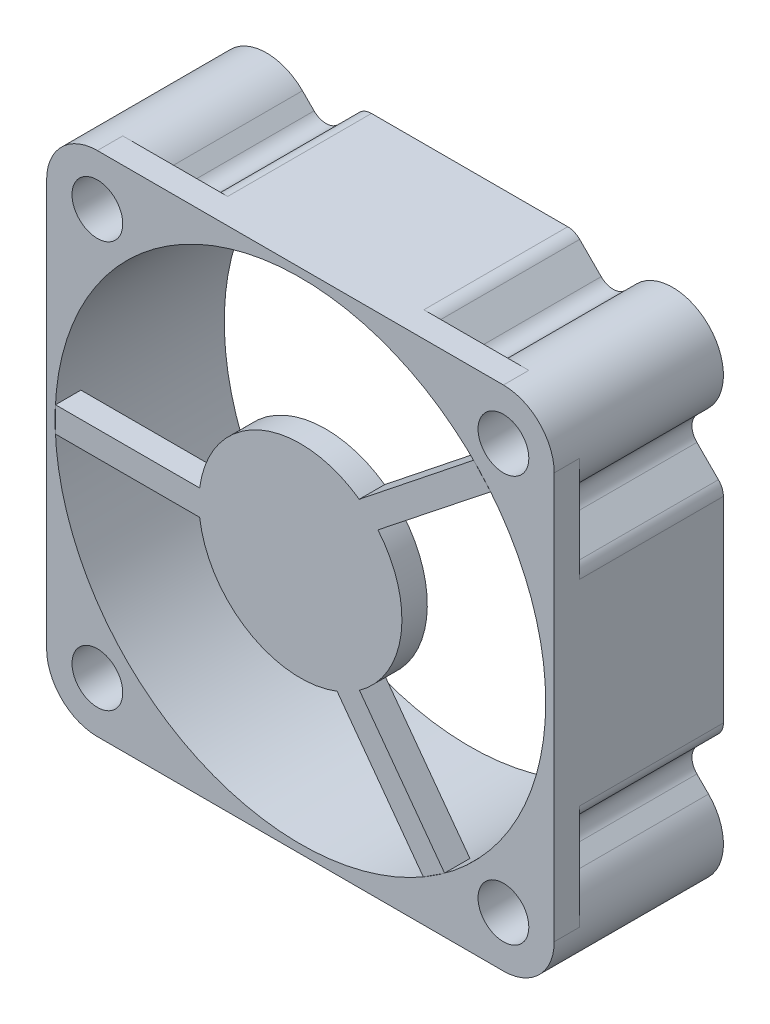
SolidWorks part; units mm, degrees
material "PBT Genel Kullanım"
ref_plane "Ön Düzlem" through (0, 0, 0) normal (0, 0, 1) x (1, 0, 0)
ref_plane "Üst Düzlem" through (0, 0, 0) normal (0, 1, 0) x (1, 0, 0)
ref_plane "Sağ Düzlem" through (0, 0, 0) normal (1, 0, 0) x (0, 0, -1)
sketch "Çizim1" plane through (0, 0, 0) normal (0, 0, 1) x (1, 0, 0)
  circle A0 centre (0, 0) radius 15
  dimension "D1" = 30
extrude "Yükseklik-Ekstrüzyon1" add sketch "Çizim1" along normal blind 10
sketch "Çizim3" plane through (0, 0, 10) normal (0, 0, 1) x (1, 0, 0)
  line L1 (-15, -15) -> (15, -15)
  line L2 (-15, -15) -> (-15, 15)
  line L3 (-15, 15) -> (15, 15)
  line L4 (15, -15) -> (15, 15)
  line L5 (-15, -15) -> (15, 15) construction
  line L6 (-15, 15) -> (15, -15) construction
  point P0 (0, 0)
  dimension "D1" = 30
  dimension "D2" = 30
extrude "Yükseklik-Ekstrüzyon2" add sketch "Çizim3" against normal blind 1.5
sketch "Çizim4" plane through (0, 0, 0) normal (0, 0, -1) x (-1, 0, 0)
  line L0 (0, 15) -> (15, 15) construction
  line L1 (-15, 15) -> (0, 15) construction
  line L2 (-15, 0) -> (-15, 15) construction
  line L3 (-15, -15) -> (-15, 0) construction
  line L4 (0, -15) -> (-15, -15) construction
  line L5 (15, -15) -> (0, -15) construction
  line L6 (15, 0) -> (15, -15) construction
  line L7 (15, 15) -> (15, 0) construction
  line L8 (0, 15) -> (15, 15)
  line L9 (-15, 15) -> (0, 15)
  line L10 (-15, 0) -> (-15, 15)
  line L11 (-15, -15) -> (-15, 0)
  line L12 (0, -15) -> (-15, -15)
  line L13 (15, -15) -> (0, -15)
  line L14 (15, 0) -> (15, -15)
  line L15 (15, 15) -> (15, 0)
extrude "Yükseklik-Ekstrüzyon3" add sketch "Çizim4" against normal blind 1.5
sketch "Çizim2" plane through (0, 0, 10) normal (0, 0, 1) x (1, 0, 0)
  circle A0 centre (0, 0) radius 14.5
  dimension "D1" = 29
extrude "Kes-Ekstrüzyon1" cut sketch "Çizim2" against normal blind 10
sketch "Çizim5" plane through (0, 0, 10) normal (0, 0, 1) x (1, 0, 0)
  circle A0 centre (0, 0) radius 6
  dimension "D1" = 12
extrude "Yükseklik-Ekstrüzyon4" add sketch "Çizim5" against normal blind 1.5 separate body
sketch "Çizim8" plane through (0, 0, 10) normal (0, 0, 1) x (1, 0, 0)
  line L0 (11.2438, 9.1557) -> (4.5817, 3.8741)
  line L1 (11.2438, 9.1557) -> (10.2378, 10.2683)
  line L2 (10.2378, 10.2683) -> (3.4776, 4.8894)
  circle A0 centre (0, 0) radius 14.5 construction
  circle A1 centre (0, 0) radius 6 construction
  circle A3 centre (0, 0) radius 6
  arc A4 (3.4776, 4.8894) -> (4.5817, 3.8741) centre (0, 0) ccw
  dimension "D1" = 1.5
  dimension "D2" = 1.5
  dimension "D3" = 0
extrude "Yükseklik-Ekstrüzyon7" add sketch "Çizim8" against normal blind 1.5
sketch "Çizim9" plane through (0, 0, 10) normal (0, 0, 1) x (1, 0, 0)
  line L0 (-14.4806, 0.75) -> (-5.9529, 0.75)
  line L1 (-14.4806, 0.75) -> (-14.4806, -0.75)
  line L2 (-14.4806, -0.75) -> (-5.9529, -0.75)
  line L6 (4.5817, 3.8741) -> (11.2438, 9.1557)
  line L7 (11.2438, 9.1557) -> (10.2378, 10.2683)
  line L8 (10.2378, 10.2683) -> (3.4776, 4.8894)
  line L9 (4.5817, 3.8741) -> (11.2438, 9.1557)
  line L10 (11.2438, 9.1557) -> (10.2378, 10.2683)
  line L11 (10.2378, 10.2683) -> (3.4776, 4.8894)
  circle A0 centre (0, 0) radius 14.5 construction
  arc A1 (3.4776, 4.8894) -> (4.5817, 3.8741) centre (0, 0) ccw construction
  arc A2 (3.4776, 4.8894) -> (-5.9529, 0.75) centre (0, 0) ccw
  arc A3 (3.4776, 4.8894) -> (4.5817, 3.8741) centre (0, 0) ccw
  arc A4 (-5.9529, -0.75) -> (4.5817, 3.8741) centre (0, 0) ccw
  dimension "D1" = 0.75
  dimension "D2" = 0
extrude "Yükseklik-Ekstrüzyon8" add sketch "Çizim9" against normal blind 1.5
sketch "Çizim10" plane through (0, 0, 10) normal (0, 0, 1) x (1, 0, 0)
  line L0 (8.5237, -11.7302) -> (3.49, -4.8806)
  line L1 (8.5237, -11.7302) -> (7.2662, -12.548)
  line L2 (7.2662, -12.548) -> (2.1704, -5.5937)
  line L9 (-5.9529, 0.75) -> (-14.4806, 0.75)
  line L10 (-14.4806, 0.75) -> (-14.4806, -0.75)
  line L11 (-14.4806, -0.75) -> (-5.9529, -0.75)
  line L12 (4.5817, 3.8741) -> (11.2438, 9.1557)
  line L13 (11.2438, 9.1557) -> (10.2378, 10.2683)
  line L14 (10.2378, 10.2683) -> (3.4776, 4.8894)
  circle A0 centre (0, 0) radius 14.5 construction
  arc A1 (-5.9529, -0.75) -> (4.5817, 3.8741) centre (0, 0) ccw construction
  arc A4 (3.4776, 4.8894) -> (-5.9529, 0.75) centre (0, 0) ccw
  arc A5 (-5.9529, -0.75) -> (4.5817, 3.8741) centre (0, 0) ccw
  arc A7 (2.1704, -5.5937) -> (3.49, -4.8806) centre (0, 0) ccw
  dimension "D1" = 1.5
  dimension "D2" = 1.5
  dimension "D3" = 0
extrude "Yükseklik-Ekstrüzyon9" add sketch "Çizim10" against normal blind 1.5
fillet "Radyus1" radius 3 8 edges at (-15, -15, 9.25) (-15, -15, 0.75) (15, -15, 9.25) (15, -15, 0.75) (15, 15, 0.75) (15, 15, 9.25) (-15, 15, 0.75) (-15, 15, 9.25)
sketch "Çizim11" plane through (0, 0, 10) normal (0, 0, 1) x (1, 0, 0)
  line L0 (-15, 12) -> (-15, -12) construction
  circle A0 centre (-12, 12) radius 1.5
  dimension "D3" = 3
  dimension "D1" = 3
  dimension "D2" = 3
extrude "Kes-Ekstrüzyon2" cut sketch "Çizim11" against normal blind 42.5
ref_plane "Düzlem1" through (0, 0, 0) normal (-1, 0, 0) x (0, 0, 1)
mirror "Aynalama1" about plane through (0, 0, 0) normal (-1, 0, 0) of "Kes-Ekstrüzyon2"
ref_plane "Düzlem2" through (0, 0, 0) normal (0, 1, 0) x (1, 0, 0)
mirror "Aynalama2" about plane through (0, 0, 0) normal (0, 1, 0) of "Aynalama1", "Kes-Ekstrüzyon2"
sketch "Sketch1" plane through (0, 0, 0) normal (0, 0, -1) x (-1, 0, 0)
  line L0 (-15, 0) -> (15, 0) construction
  line L1 (-15, 12) -> (-15, -12) construction
  line L2 (15, -12) -> (15, 12) construction
  line L3 (0, 15) -> (0, -15) construction
  line L4 (-12, -15) -> (12, -15) construction
  line L5 (-15, 6.2132) -> (-6.2132, 15) construction
  line L7 (12, 15) -> (-12, 15) construction
  line L8 (-8.4853, 12.7279) -> (-9.8787, 14.1213)
  line L9 (-12.7279, 8.4853) -> (-14.1213, 9.8787)
  line L10 (-8.4853, 12.7279) -> (-6.2132, 15)
  line L11 (-6.2132, 15) -> (-12, 15)
  line L12 (-12.7279, 8.4853) -> (-15, 6.2132)
  line L13 (-15, 6.2132) -> (-15, 12)
  line L14 (-6.2132, -15) -> (-12, -15)
  line L15 (-8.4853, -12.7279) -> (-6.2132, -15)
  line L16 (-8.4853, -12.7279) -> (-9.8787, -14.1213)
  line L17 (-12.7279, -8.4853) -> (-14.1213, -9.8787)
  line L18 (-15, -6.2132) -> (-15, -12)
  line L19 (-12.7279, -8.4853) -> (-15, -6.2132)
  line L20 (6.2132, 15) -> (12, 15)
  line L21 (8.4853, 12.7279) -> (6.2132, 15)
  line L22 (8.4853, 12.7279) -> (9.8787, 14.1213)
  line L23 (12.7279, 8.4853) -> (15, 6.2132)
  line L24 (12.7279, 8.4853) -> (14.1213, 9.8787)
  line L25 (15, 6.2132) -> (15, 12)
  line L26 (12.7279, -8.4853) -> (15, -6.2132)
  line L27 (15, -6.2132) -> (15, -12)
  line L28 (12.7279, -8.4853) -> (14.1213, -9.8787)
  line L29 (8.4853, -12.7279) -> (9.8787, -14.1213)
  line L30 (8.4853, -12.7279) -> (6.2132, -15)
  line L31 (6.2132, -15) -> (12, -15)
  circle A0 centre (-12, 12) radius 3 construction
  arc A1 (-12, 15) -> (-15, 12) centre (-12, 12) ccw construction
  arc A3 (-15, 12) -> (-14.1213, 9.8787) centre (-12, 12) ccw
  circle A4 centre (0, 0) radius 15
  circle A5 centre (0, 0) radius 15 construction
  arc A6 (-12, 15) -> (-9.8787, 14.1213) centre (-12, 12) cw
  arc A7 (-12, -15) -> (-9.8787, -14.1213) centre (-12, -12) ccw
  arc A8 (-15, -12) -> (-14.1213, -9.8787) centre (-12, -12) cw
  arc A9 (12, 15) -> (9.8787, 14.1213) centre (12, 12) ccw
  arc A10 (15, 12) -> (14.1213, 9.8787) centre (12, 12) cw
  arc A11 (15, -12) -> (14.1213, -9.8787) centre (12, -12) ccw
  arc A12 (12, -15) -> (9.8787, -14.1213) centre (12, -12) cw
  dimension "D2" = 45
  dimension "D1" = 0.5
extrude "Cut-Extrude1" cut sketch "Sketch1" against normal up to surface (1.5 mm away) up to face at (11.432, 11.432, 1.5)
sketch "Sketch2" plane through (0, 0, 8.5) normal (0, 0, -1) x (-1, 0, 0)
  line L40 (9.8787, 14.1213) -> (8.4853, 12.7279)
  line L41 (8.4853, 12.7279) -> (6.2132, 15)
  line L42 (6.2132, 15) -> (-6.2132, 15)
  line L43 (-6.2132, 15) -> (-8.4853, 12.7279)
  line L44 (-8.4853, 12.7279) -> (-9.8787, 14.1213)
  line L45 (-14.1213, 9.8787) -> (-12.7279, 8.4853)
  line L46 (-12.7279, 8.4853) -> (-15, 6.2132)
  line L47 (-15, 6.2132) -> (-15, -6.2132)
  line L48 (-15, -6.2132) -> (-12.7279, -8.4853)
  line L49 (-12.7279, -8.4853) -> (-14.1213, -9.8787)
  line L50 (-9.8787, -14.1213) -> (-8.4853, -12.7279)
  line L51 (-8.4853, -12.7279) -> (-6.2132, -15)
  line L52 (-6.2132, -15) -> (6.2132, -15)
  line L53 (6.2132, -15) -> (8.4853, -12.7279)
  line L54 (8.4853, -12.7279) -> (9.8787, -14.1213)
  line L55 (14.1213, -9.8787) -> (12.7279, -8.4853)
  line L56 (12.7279, -8.4853) -> (15, -6.2132)
  line L57 (15, -6.2132) -> (15, 6.2132)
  line L58 (15, 6.2132) -> (12.7279, 8.4853)
  line L59 (12.7279, 8.4853) -> (14.1213, 9.8787)
  line L60 (9.8787, 14.1213) -> (8.4853, 12.7279)
  line L61 (8.4853, 12.7279) -> (6.2132, 15)
  line L62 (6.2132, 15) -> (-6.2132, 15)
  line L63 (-6.2132, 15) -> (-8.4853, 12.7279)
  line L64 (-8.4853, 12.7279) -> (-9.8787, 14.1213)
  line L65 (-14.1213, 9.8787) -> (-12.7279, 8.4853)
  line L66 (-12.7279, 8.4853) -> (-15, 6.2132)
  line L67 (-15, 6.2132) -> (-15, -6.2132)
  line L68 (-15, -6.2132) -> (-12.7279, -8.4853)
  line L69 (-12.7279, -8.4853) -> (-14.1213, -9.8787)
  line L70 (-9.8787, -14.1213) -> (-8.4853, -12.7279)
  line L71 (-8.4853, -12.7279) -> (-6.2132, -15)
  line L72 (-6.2132, -15) -> (6.2132, -15)
  line L73 (6.2132, -15) -> (8.4853, -12.7279)
  line L74 (8.4853, -12.7279) -> (9.8787, -14.1213)
  line L75 (14.1213, -9.8787) -> (12.7279, -8.4853)
  line L76 (12.7279, -8.4853) -> (15, -6.2132)
  line L77 (15, -6.2132) -> (15, 6.2132)
  line L78 (15, 6.2132) -> (12.7279, 8.4853)
  line L79 (12.7279, 8.4853) -> (14.1213, 9.8787)
  circle A6 centre (0, 0) radius 14.5
  circle A7 centre (0, 0) radius 14.5
  arc A8 (14.1213, 9.8787) -> (9.8787, 14.1213) centre (12, 12) ccw
  arc A9 (-9.8787, 14.1213) -> (-14.1213, 9.8787) centre (-12, 12) ccw
  arc A10 (-14.1213, -9.8787) -> (-9.8787, -14.1213) centre (-12, -12) ccw
  arc A11 (9.8787, -14.1213) -> (14.1213, -9.8787) centre (12, -12) ccw
  arc A12 (14.1213, 9.8787) -> (9.8787, 14.1213) centre (12, 12) ccw
  arc A13 (-9.8787, 14.1213) -> (-14.1213, 9.8787) centre (-12, 12) ccw
  arc A14 (-14.1213, -9.8787) -> (-9.8787, -14.1213) centre (-12, -12) ccw
  arc A15 (9.8787, -14.1213) -> (14.1213, -9.8787) centre (12, -12) ccw
  circle A17 centre (-12, 12) radius 1.5
  circle A18 centre (-12, 12) radius 1.5
  circle A20 centre (12, 12) radius 1.5
  circle A21 centre (12, 12) radius 1.5
  circle A27 centre (12, -12) radius 1.5
  circle A28 centre (12, -12) radius 1.5
  circle A30 centre (-12, -12) radius 1.5
  circle A31 centre (-12, -12) radius 1.5
  dimension "D1" = 0
  dimension "D2" = 0
  dimension "D3" = 0
  dimension "D4" = 0
  dimension "D5" = 0
  dimension "D6" = 0
extrude "Boss-Extrude1" add sketch "Sketch2" along normal up to surface (7 mm away) up to face at (10.8318, 10.8318, 1.5)
fillet "Fillet1" radius 1 15 edges at (15, 6.2132, 4.25) (8.4853, 12.7279, 4.25) (-8.4853, 12.7279, 4.25) (-12.7279, -8.4853, 4.25) (-8.4853, -12.7279, 4.25) (8.4853, -12.7279, 4.25) (12.7279, -8.4853, 4.25) (12.7279, 8.4853, 4.25) (15, -6.2132, 4.25) (6.2132, -15, 4.25) (-6.2132, -15, 4.25) (-15, -6.2132, 4.25) (-15, 6.2132, 4.25) (-6.2132, 15, 4.25) (6.2132, 15, 4.25)
